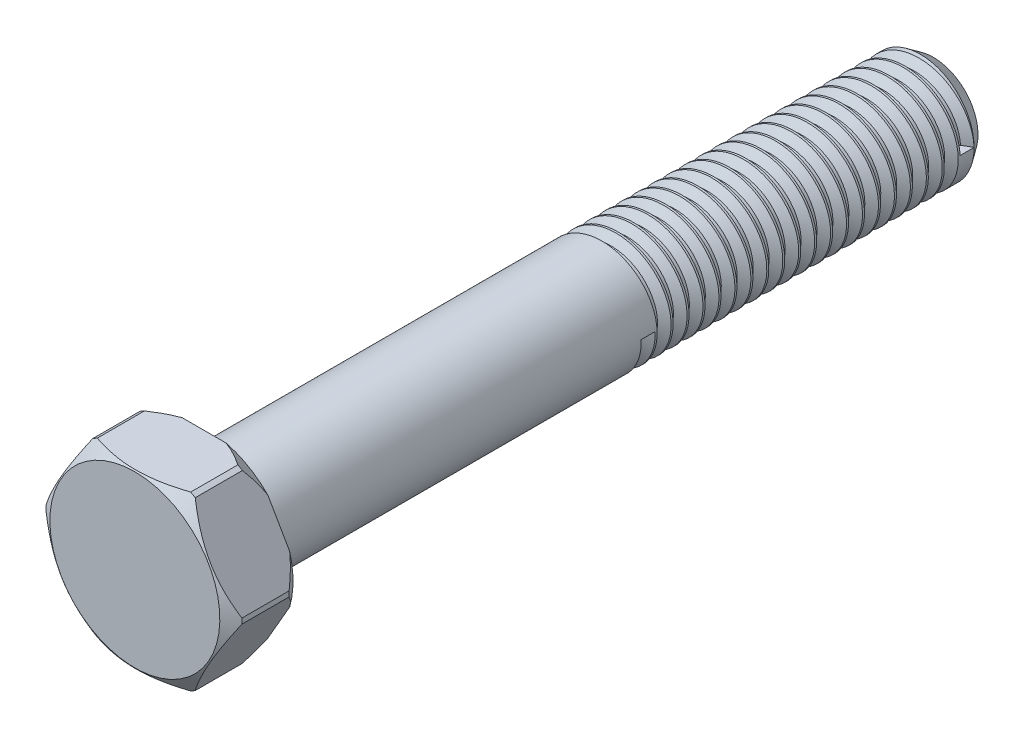
SolidWorks part; units mm, degrees
material "Malleable Cast Iron"
ref_plane "Front Plane" through (0, 0, 0) normal (0, 0, 1) x (1, 0, 0)
ref_plane "Top Plane" through (0, 0, 0) normal (0, 1, 0) x (1, 0, 0)
ref_plane "Right Plane" through (0, 0, 0) normal (1, 0, 0) x (0, 0, -1)
sketch "Sketch7" plane through (0, 0, 0) normal (1, 0, 0) x (0, 0, -1)
  line L0 (-50, 0) -> (50, 0) construction
  line L1 (-43.8, 0) -> (-43.8, 10.75)
  line L2 (-43.8, 10.75) -> (-36.2, 10.75)
  line L3 (-36.2, 10.75) -> (-36.2, 5.9)
  line L4 (-36.2, 5.9) -> (43.8, 5.9)
  line L5 (43.8, 5.9) -> (43.8, 0)
  line L6 (43.8, 0) -> (-43.8, 0)
  dimension "D1" = 100
  dimension "D2" = 80
  dimension "D3" = 7.6
  dimension "D4" = 21.5
  dimension "D5" = 11.8
revolve "Revolve1" add sketch "Sketch7" angle 360 about L0
chamfer "Chamfer1" distance 1 angle 55 3 edges at (0, -10.75, 36.2) (0, -10.75, 43.8) (0, -5.9, -43.8) first distance on face at (0, -10.75, 36.2) first distance on face at (0, -10.75, 43.8) first distance on face at (0, -5.9, -43.8)
sketch "Sketch8" plane through (0, 0, 43.8) normal (0, 0, 1) x (1, 0, 0)
  line L0 (0, 0) -> (10.9119, 0) construction
  line L1 (10.9119, 0) -> (5.456, 9.45)
  line L2 (5.456, 9.45) -> (-5.456, 9.45)
  line L3 (-5.456, 9.45) -> (-10.9119, 0)
  line L4 (-10.9119, 0) -> (-5.456, -9.45)
  line L5 (-5.456, -9.45) -> (5.456, -9.45)
  line L6 (5.456, -9.45) -> (10.9119, 0)
  circle A0 centre (0, 0) radius 9.45 construction
  dimension "D1" = 18.9
extrude "Cut-Extrude1" cut sketch "Sketch8" against normal blind 10 flip side to cut
thread "Thread1" pitch 1.75 method cut profile "Thread Profile1" start angle 0, offset 0, length 35, pitch 1.75, diameter 11.8
ref_plane "Plane4" through (5.9, 0, -42.3719) normal (0, -1, 0) x (1, 0, 0)
sketch "Thread Profile1" plane through (5.9, 0, -42.3719) normal (0, -1, 0) x (1, 0, 0)
  line L0 (0, 0) -> (0, 1.75) construction
  line L11 (0, 0) -> (0, 1.5312)
  line L12 (0, 1.5312) -> (-0.9472, 0.9844)
  line L13 (-0.9472, 0.9844) -> (-0.9472, 0.5469)
  line L15 (-0.9472, 0.5469) -> (0, 0)
  line L17 (-0.9472, 0.7656) -> (0, 0.7656) construction
  point P2 (0, 0)
  dimension "Pitch" = 1.75
  dimension "Profile_Angle" = 60
  dimension "Profile_Land" = 0.4375
  dimension "Profile_Height" = 0.9472
